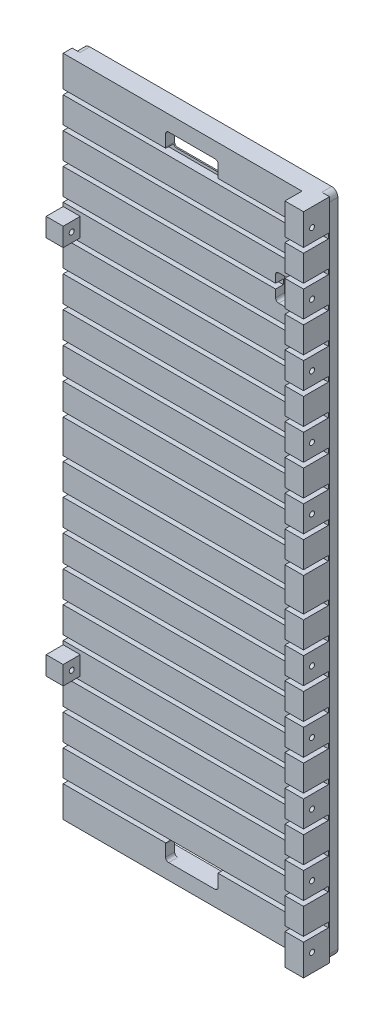
SolidWorks part; units mm, degrees
ref_plane "Front Plane" through (0, 0, 0) normal (0, 0, 1) x (1, 0, 0)
ref_plane "Top Plane" through (0, 0, 0) normal (0, 1, 0) x (1, 0, 0)
ref_plane "Right Plane" through (0, 0, 0) normal (1, 0, 0) x (0, 0, -1)
sketch "Sketch1" plane through (0, 0, 0) normal (0, 0, 1) x (1, 0, 0)
  line L1 (-41.5, -107) -> (41.5, -107)
  line L2 (-41.5, -107) -> (-41.5, 107)
  line L3 (-41.5, 107) -> (41.5, 107)
  line L4 (41.5, -107) -> (41.5, 107)
  line L5 (-41.5, -107) -> (41.5, 107) construction
  line L6 (-41.5, 107) -> (41.5, -107) construction
  point P0 (0, 0)
  dimension "D1" = 83
  dimension "D2" = 214
extrude "Boss-Extrude1" add sketch "Sketch1" along normal blind 8.4
sketch "Sketch2" plane through (0, 107, 0) normal (0, 1, 0) x (1, 0, 0)
  line L0 (41.5, -8.4) -> (41.5, 0) construction
  line L1 (-41.5, -8.4) -> (35.5, -8.4)
  line L2 (-41.5, -8.4) -> (-41.5, -2.9)
  line L3 (-41.5, -2.9) -> (35.5, -2.9)
  line L4 (35.5, -8.4) -> (35.5, -2.9)
  dimension "D1" = 5.5
  dimension "D2" = 6
extrude "Cut-Extrude1" cut sketch "Sketch2" against normal through all
sketch "Sketch3" plane through (41.5, 0, 0) normal (1, 0, 0) x (0, 0, -1)
  line L0 (-8.4, -107) -> (-8.4, 107) construction
  line L1 (-8.4, 97) -> (-0.4, 97)
  line L2 (-8.4, 97) -> (-8.4, 95.4)
  line L3 (-8.4, 95.4) -> (-0.4, 95.4)
  line L4 (-0.4, 97) -> (-0.4, 95.4)
  line L5 (-8.4, 107) -> (0, 107) construction
  dimension "D1" = 1.6
  dimension "D2" = 8
  dimension "D3" = 10
extrude "Cut-Extrude2" cut sketch "Sketch3" against normal through all
pattern_linear "LPattern1" count 10 spacing 10 along (0, -1, 0) of "Cut-Extrude2"
mirror "Mirror1" about plane through (0, 0, 0) normal (0, 1, 0) of "LPattern1"
sketch "Sketch4" plane through (0, 0, 0) normal (0, 0, -1) x (-1, 0, 0)
  line L0 (-41.5, 107) -> (41.5, 107) construction
  line L1 (-39, 107) -> (39, 107)
  line L2 (-41, 105) -> (-41, -105)
  line L3 (-39, -107) -> (39, -107)
  line L4 (41, 105) -> (41, -105)
  line L5 (-33.5, -102) -> (33.5, -102)
  line L6 (-35.5, -100) -> (-35.5, 100)
  line L7 (-33.5, 102) -> (33.5, 102)
  line L8 (35.5, -100) -> (35.5, 100)
  line L9 (-35.5, -102) -> (35.5, 102) construction
  line L10 (-35.5, 102) -> (35.5, -102) construction
  line L11 (41.5, -107) -> (-41.5, -107) construction
  arc A0 (-41, -105) -> (-39, -107) centre (-39, -105) ccw
  arc A1 (39, -107) -> (41, -105) centre (39, -105) ccw
  arc A2 (39, 107) -> (41, 105) centre (39, 105) cw
  arc A3 (-39, 107) -> (-41, 105) centre (-39, 105) ccw
  arc A4 (33.5, -102) -> (35.5, -100) centre (33.5, -100) ccw
  arc A5 (-33.5, -102) -> (-35.5, -100) centre (-33.5, -100) cw
  arc A6 (-35.5, 100) -> (-33.5, 102) centre (-33.5, 100) cw
  arc A7 (33.5, 102) -> (35.5, 100) centre (33.5, 100) cw
  point P10 (41.5, -107)
  point P15 (-41.5, 107)
  point P16 (0, 0)
  dimension "D1" = 2
  dimension "D4" = 2
  dimension "D2" = 5
  dimension "D3" = 5.5
  dimension "D5" = 41
  dimension "D6" = 41
extrude "Boss-Extrude2" add sketch "Sketch4" along normal blind 3.18
sketch "Sketch5" plane through (0, 0, 2.9) normal (0, 0, 1) x (1, 0, 0)
  line L0 (-41.5, 57) -> (-41.5, 65.4) construction
  line L1 (-36, 58.2) -> (-41.5, 58.2)
  line L2 (-36, 58.2) -> (-36, 64.2)
  line L3 (-36, 64.2) -> (-41.5, 64.2)
  line L4 (-41.5, 58.2) -> (-41.5, 64.2)
  line L5 (-36, 58.2) -> (-41.5, 64.2) construction
  line L6 (-36, 64.2) -> (-41.5, 58.2) construction
  line L8 (35.5, 65.4) -> (-41.5, 65.4) construction
  point P0 (-38.75, 61.2)
  dimension "D1" = 6
  dimension "D2" = 5.5
  dimension "D3" = 4.2
extrude "Boss-Extrude3" add sketch "Sketch5" along normal blind 5.5
mirror "Mirror2" about plane through (0, 0, 0) normal (0, 1, 0) of "Boss-Extrude3"
sketch "Sketch6" plane through (0, 0, 0) normal (0, 0, -1) x (-1, 0, 0)
  line L0 (33.5, 102) -> (-33.5, 102) construction
  line L1 (-7.475, 96.3) -> (7.475, 96.3)
  line L2 (-8.475, 97.3) -> (-8.475, 101)
  line L3 (-7.475, 102) -> (7.475, 102)
  line L4 (8.475, 97.3) -> (8.475, 101)
  line L5 (-8.475, 96.3) -> (8.475, 102) construction
  line L6 (-8.475, 102) -> (8.475, 96.3) construction
  arc A0 (-8.475, 101) -> (-7.475, 102) centre (-7.475, 101) cw
  arc A1 (7.475, 102) -> (8.475, 101) centre (7.475, 101) cw
  arc A2 (7.475, 96.3) -> (8.475, 97.3) centre (7.475, 97.3) ccw
  arc A3 (-7.475, 96.3) -> (-8.475, 97.3) centre (-7.475, 97.3) cw
  point P0 (0, 99.15)
  dimension "D3" = 1
  dimension "D1" = 5.7
  dimension "D2" = 16.95
extrude "Cut-Extrude3" cut sketch "Sketch6" against normal through all
mirror "Mirror3" about plane through (0, 0, 0) normal (0, 1, 0) of "Cut-Extrude3"
hole_wizard "M2x0.4 Tapped Hole1" positions "Sketch8" profile "Sketch7" tap size "M2x0.4" standard "ANSI Metric" end condition through all
sketch "Sketch8" plane through (41.5, 0, 0) normal (1, 0, 0) x (0, 0, -1)
  line L0 (-8.4, 97) -> (-8.4, 107) construction
  line L1 (-8.4, 107) -> (0, 107) construction
  line L2 (0, 0) -> (-25.7972, 0) construction
  line L3 (0, -107) -> (0, 107) construction
  point P0 (-5.65, 101.2)
  point P16 (-5.65, 81.2)
  point P17 (-5.65, 61.2)
  point P18 (-5.65, 41.2)
  point P19 (-5.65, 21.2)
  point P34 (-5.65, -101.2)
  point P35 (-5.65, -81.2)
  point P36 (-5.65, -61.2)
  point P37 (-5.65, -41.2)
  point P38 (-5.65, -21.2)
  dimension "D1" = 2.75
  dimension "D2" = 5.8
  dimension "D3" = 5
sketch "Sketch7" plane through (41.5, 101.2, 5.65) normal (0, 1, 0) x (0, 0, -1)
  line L0 (0, 0) -> (0, 83)
  line L1 (0, 83) -> (0.8, 83)
  line L2 (0.8, 83) -> (0.8, 0)
  line L5 (0.8, 0) -> (0, 0)
  line L11 (0, -6.35) -> (0, 107.95) construction
  dimension "Thread Major Dia." = 1.6
  dimension "Thru Tap Drill Depth" = 83
hole_wizard "M2x0.4 Tapped Hole2" positions "Sketch10" profile "Sketch11" tap size "M2x0.4" standard "ANSI Metric"
sketch "Sketch10" plane through (0, 0, -3.18) normal (0, 0, -1) x (-1, 0, 0)
  line L0 (39, 107) -> (-39, 107) construction
  line L1 (-41, 105) -> (-41, -105) construction
  line L3 (-35.5, 0) -> (35.5, 0) construction
  line L4 (-35.5, 100) -> (-35.5, -100) construction
  line L5 (35.5, -100) -> (35.5, 100) construction
  point P0 (-37.5, 101.2)
  point P15 (37.5, 101.2)
  point P16 (37.5, 81.2)
  point P17 (37.5, 61.2)
  point P18 (37.5, 41.2)
  point P19 (37.5, 21.2)
  point P20 (-37.5, 81.2)
  point P21 (-37.5, 61.2)
  point P22 (-37.5, 41.2)
  point P23 (-37.5, 21.2)
  point P32 (37.5, -101.2)
  point P33 (-37.5, -21.2)
  point P34 (-37.5, -41.2)
  point P35 (-37.5, -61.2)
  point P36 (-37.5, -81.2)
  point P37 (37.5, -21.2)
  point P38 (37.5, -41.2)
  point P39 (37.5, -61.2)
  point P40 (37.5, -81.2)
  point P41 (-37.5, -101.2)
  dimension "D1" = 5.8
  dimension "D2" = 3.5
  dimension "D5" = 2
  dimension "D3" = 5
sketch "Sketch11" plane through (37.5, 101.2, -3.18) normal (1, 0, 0) x (0, 1, 0)
  line L0 (0, 0) -> (0, 4.4807)
  line L1 (0, 4.4807) -> (0.8, 4)
  line L2 (0.8, 4) -> (0.8, 0)
  line L5 (0.8, 0) -> (0, 0)
  line L10 (0, 4.4807) -> (-0.8, 4) construction
  line L11 (0, -6.35) -> (0, 107.95) construction
  dimension "Tap Drill Dia." = 1.6
  dimension "Tap Drill Depth" = 4
  dimension "Drill Angle" = 118
sketch "Sketch12" plane through (0, 0, 2.9) normal (0, 0, 1) x (1, 0, 0)
  line L1 (28, 71.95) -> (34.5, 71.95)
  line L2 (27, 72.95) -> (27, 79.45)
  line L3 (28, 80.45) -> (34.5, 80.45)
  line L4 (35.5, 72.95) -> (35.5, 79.45)
  line L5 (-35.714, 77) -> (-35.714, 75.4) construction
  line L6 (-41.5, 77) -> (35.5, 77) construction
  line L7 (35.5, 75.4) -> (-41.5, 75.4) construction
  line L8 (41.5, 67) -> (41.5, 75.4) construction
  arc A0 (35.5, 72.95) -> (34.5, 71.95) centre (34.5, 72.95) cw
  arc A1 (34.5, 80.45) -> (35.5, 79.45) centre (34.5, 79.45) cw
  arc A2 (27, 79.45) -> (28, 80.45) centre (28, 79.45) cw
  arc A3 (27, 72.95) -> (28, 71.95) centre (28, 72.95) ccw
  point P6 (27, 76.2)
  point P19 (-35.714, 76.2)
  dimension "D1" = 1
  dimension "D2" = 8.5
  dimension "D3" = 8.5
  dimension "D4" = 6
extrude "Cut-Extrude4" cut sketch "Sketch12" against normal blind 10
